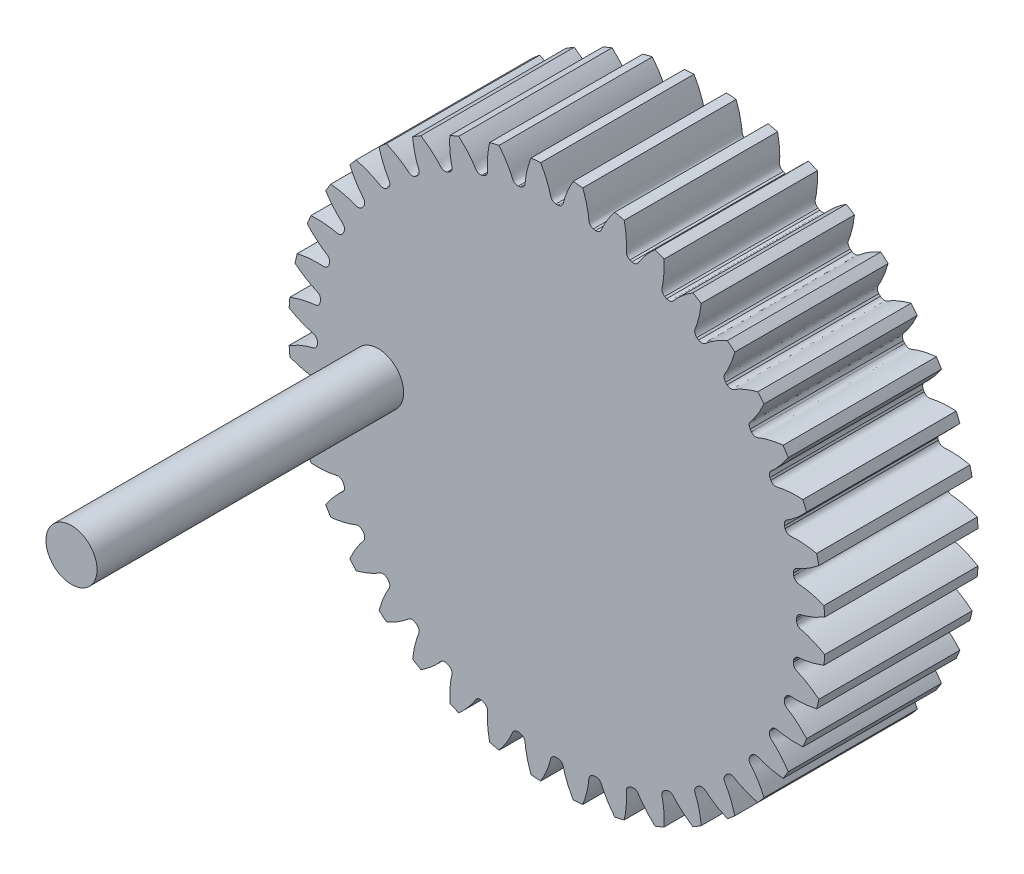
SolidWorks part; units mm, degrees
ref_plane "前视基准面" through (0, 0, 0) normal (0, 0, 1) x (1, 0, 0)
ref_plane "上视基准面" through (0, 0, 0) normal (0, 1, 0) x (1, 0, 0)
ref_plane "右视基准面" through (0, 0, 0) normal (1, 0, 0) x (0, 0, -1)
sketch "草图1" plane through (0, 0, 0) normal (0, 0, 1) x (1, 0, 0)
  circle A0 centre (0, 0) radius 52.5
extrude "凸台-拉伸1" add sketch "草图1" along normal blind 30
ref_axis "基准轴1" through (0, 0, 30) along (0, 0, -1)
sketch "草图2" plane through (0, 0, 0) normal (0, 0, 1) x (1, 0, 0)
  line L0 (0, 0) -> (0, 52.5) construction
  circle A0 centre (0, 0) radius 52.5 construction
  arc A1 (0.2115, 46.8745) -> (-0.2115, 46.8745) centre (0, 0) ccw
  arc A2 (9.1853, 59.695) -> (-9.1853, 59.695) centre (0, 0) ccw
  spline S0 degree 3 poles (0.2115, 46.8745) (1.1392, 47.0101) (1.2237, 47.6762) (1.4174, 48.3905) (1.4848, 48.6232) (1.5626, 48.8723) (1.6513, 49.1377) (1.7515, 49.4189) (1.864, 49.7157) (1.9895, 50.0276) (2.1285, 50.3542) (2.2817, 50.6952) (2.4498, 51.05) (2.6333, 51.4181) (2.8328, 51.7992) (3.0489, 52.1927) (3.2823, 52.5981) (3.5334, 53.0148) (3.8028, 53.4423) (4.0911, 53.8801) (4.3986, 54.3275) (4.7261, 54.7839) (5.0738, 55.2488) (5.4423, 55.7214) (5.8321, 56.2011) (6.2435, 56.6873) (6.677, 57.1793) (7.1329, 57.6763) (7.6116, 58.1778) (8.2897, 58.8601) (8.8205, 59.3628) (9.1853, 59.695) knots 0 0 0 0 0.110657 0.124739 0.140005 0.156457 0.174093 0.192913 0.212918 0.234108 0.256483 0.280042 0.304786 0.330714 0.357827 0.386125 0.415607 0.446274 0.478126 0.511162 0.545383 0.580789 0.617379 0.655154 0.694113 0.734257 0.775586 0.8181 0.861798 0.906681 1 1 1 1
  spline S1 degree 3 poles (-0.2115, 46.8745) (-1.1392, 47.0101) (-1.2237, 47.6762) (-1.4174, 48.3905) (-1.4848, 48.6232) (-1.5626, 48.8723) (-1.6513, 49.1377) (-1.7515, 49.4189) (-1.864, 49.7157) (-1.9895, 50.0276) (-2.1285, 50.3542) (-2.2817, 50.6952) (-2.4498, 51.05) (-2.6333, 51.4181) (-2.8328, 51.7992) (-3.0489, 52.1927) (-3.2823, 52.5981) (-3.5334, 53.0148) (-3.8028, 53.4423) (-4.0911, 53.8801) (-4.3986, 54.3275) (-4.7261, 54.7839) (-5.0738, 55.2488) (-5.4423, 55.7214) (-5.8321, 56.2011) (-6.2435, 56.6873) (-6.677, 57.1793) (-7.1329, 57.6763) (-7.6116, 58.1778) (-8.2897, 58.8601) (-8.8205, 59.3628) (-9.1853, 59.695) knots 0 0 0 0 0.110657 0.124739 0.140005 0.156457 0.174093 0.192913 0.212918 0.234108 0.256483 0.280042 0.304786 0.330714 0.357827 0.386125 0.415607 0.446274 0.478126 0.511162 0.545383 0.580789 0.617379 0.655154 0.694113 0.734257 0.775586 0.8181 0.861798 0.906681 1 1 1 1
extrude "切除-拉伸1" cut sketch "草图2" along normal through all
pattern_circular "阵列(圆周)1" count 40 every 9 about axis through (0, 0, 30) along (0, 0, -1) of "切除-拉伸1"
sketch "草图3" plane through (0, 0, 0) normal (0, 0, 1) x (1, 0, 0)
  circle A0 centre (0, 0) radius 50 construction
  dimension "Dn" = 100
sketch "草图4" plane through (0, 0, 30) normal (0, 0, 1) x (1, 0, 0)
  line L0 (0, 0) -> (0, 16.8095)
  point P4 (0, 0)
sketch "草图5" plane through (0, 0, 30) normal (0, 0, 1) x (1, 0, 0)
  circle A0 centre (-35, 0) radius 5
  dimension "D1" = 10
  dimension "D2" = 35
extrude "凸台-拉伸2" add sketch "草图5" along normal blind 60
